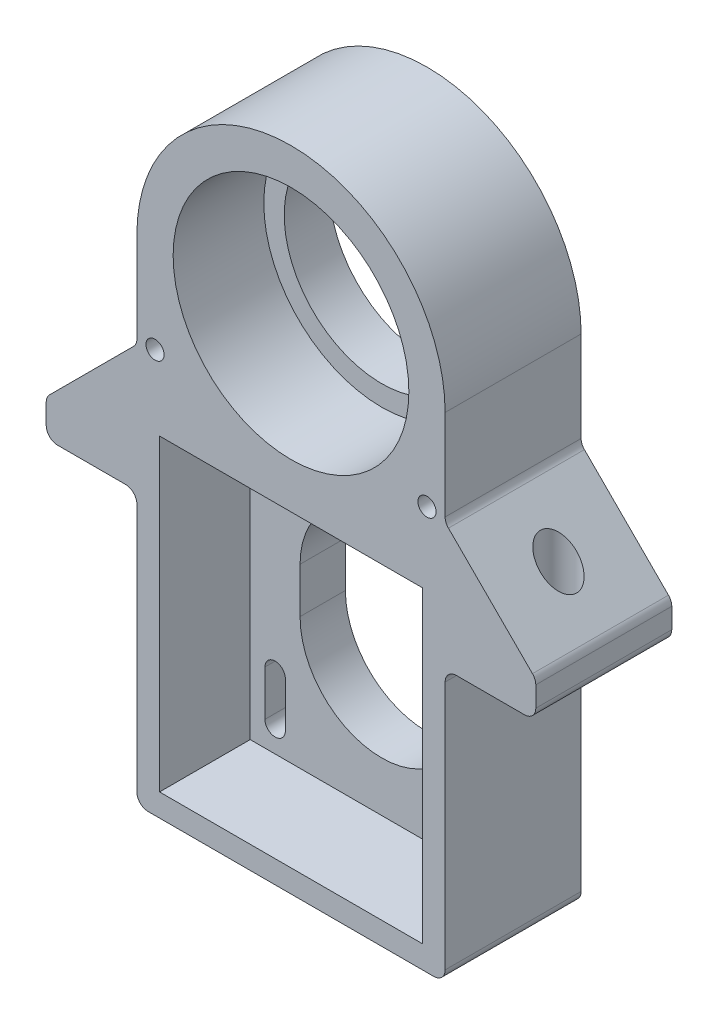
SolidWorks part; units mm, degrees
note: The reader was unsure of these and kept them because the rebuilt part matched: shared geometry of "Esquisse1<4>".
ref_plane "Plan de face" through (0, 0, 0) normal (0, 0, 1) x (1, 0, 0)
ref_plane "Plan de dessus" through (0, 0, 0) normal (0, 1, 0) x (1, 0, 0)
ref_plane "Plan de droite" through (0, 0, 0) normal (1, 0, 0) x (0, 0, -1)
sketch "Esquisse1" plane through (0, 0, 0) normal (0, 0, 1) x (1, 0, 0)
  line L0 (0, 0) -> (0, -75) construction
  line L1 (-34, 0) -> (-34, -41)
  line L2 (29, -104) -> (-29, -104)
  line L3 (29, -104) -> (29, -46)
  line L4 (29, -46) -> (-29, -46)
  line L5 (-29, -104) -> (-29, -46)
  line L6 (29, -104) -> (-29, -46) construction
  line L7 (29, -46) -> (-29, -104) construction
  line L8 (23.5, -98.5) -> (-23.5, -98.5)
  line L9 (23.5, -98.5) -> (23.5, -51.5)
  line L10 (23.5, -51.5) -> (-23.5, -51.5)
  line L11 (-23.5, -98.5) -> (-23.5, -51.5)
  line L12 (23.5, -98.5) -> (-23.5, -51.5) construction
  line L13 (23.5, -51.5) -> (-23.5, -98.5) construction
  line L14 (34, -109) -> (-34, -109)
  line L15 (34, -109) -> (34, -41)
  line L16 (34, -41) -> (-34, -41)
  line L17 (-34, -109) -> (-34, -41)
  line L18 (34, -109) -> (-34, -41) construction
  line L19 (34, -41) -> (-34, -109) construction
  line L20 (34, 0) -> (34, -41)
  line L21 (-34, -41) -> (34, -41)
  line L22 (26, 0) -> (34, -41)
  line L23 (-34, -41) -> (-54, -41)
  line L24 (-34, -41) -> (-34, -49)
  line L25 (-34, -49) -> (-54, -49)
  line L26 (-54, -41) -> (-54, -49)
  line L27 (34, -41) -> (54, -41)
  line L28 (34, -41) -> (34, -49)
  line L29 (34, -49) -> (54, -49)
  line L30 (54, -41) -> (54, -49)
  line L31 (-34, -41) -> (-26, 0)
  line L32 (-26, 0) -> (26, 0)
  line L33 (15, 0) -> (18, -75)
  line L34 (18, -75) -> (-18, -75)
  line L35 (-18, -75) -> (-15, 0)
  line L36 (30.5, 0) -> (18, -75)
  line L37 (-30.5, 0) -> (-18, -75)
  line L38 (-54, -41) -> (-34, -21)
  line L39 (54, -41) -> (34, -21)
  line L40 (23.5, -98.5) -> (23.5, -88.5) construction
  line L41 (21.25, -98.5) -> (21.25, -88.5)
  line L42 (25.75, -98.5) -> (25.75, -88.5)
  line L43 (23.5, -51.5) -> (23.5, -41.5) construction
  line L44 (21.25, -51.5) -> (21.25, -41.5)
  line L45 (25.75, -51.5) -> (25.75, -41.5)
  line L46 (-23.5, -51.5) -> (-23.5, -41.5) construction
  line L47 (-21.25, -51.5) -> (-21.25, -41.5)
  line L48 (-25.75, -51.5) -> (-25.75, -41.5)
  line L49 (-23.5, -98.5) -> (-23.5, -88.5) construction
  line L50 (-21.25, -98.5) -> (-21.25, -88.5)
  line L51 (-25.75, -98.5) -> (-25.75, -88.5)
  line L52 (0, -75) -> (0, -65) construction
  line L53 (-18, -75) -> (-18, -65)
  line L54 (18, -75) -> (18, -65)
  line L56 (29, -46) -> (-29, -46)
  line L57 (29, -46) -> (29, -36)
  line L58 (29, -36) -> (-29, -36)
  line L59 (-29, -46) -> (-29, -36)
  line L60 (34, -41) -> (-34, -41)
  line L61 (34, -41) -> (34, -31)
  line L62 (34, -31) -> (-34, -31)
  line L63 (-34, -41) -> (-34, -31)
  circle A0 centre (0, 0) radius 26
  circle A1 centre (0, 0) radius 34
  circle A2 centre (0, -75) radius 18
  circle A3 centre (0, 0) radius 21.5
  circle A4 centre (23.5, -51.5) radius 2.25
  circle A5 centre (23.5, -98.5) radius 2.25
  circle A6 centre (-23.5, -98.5) radius 2.25
  circle A7 centre (-23.5, -51.5) radius 2.25
  circle A8 centre (0, 0) radius 15
  circle A9 centre (-30, -20) radius 2
  circle A10 centre (30, -20) radius 2
  circle A11 centre (0, 0) radius 30.5
  circle A12 centre (-30, -20) radius 2
  circle A13 centre (30, -20) radius 2
  arc A14 (21.25, -98.5) -> (25.75, -98.5) centre (23.5, -98.5) ccw
  arc A15 (25.75, -88.5) -> (21.25, -88.5) centre (23.5, -88.5) ccw
  arc A16 (21.25, -51.5) -> (25.75, -51.5) centre (23.5, -51.5) ccw
  arc A17 (25.75, -41.5) -> (21.25, -41.5) centre (23.5, -41.5) ccw
  arc A18 (-21.25, -51.5) -> (-25.75, -51.5) centre (-23.5, -51.5) cw
  arc A19 (-25.75, -41.5) -> (-21.25, -41.5) centre (-23.5, -41.5) cw
  arc A20 (-21.25, -98.5) -> (-25.75, -98.5) centre (-23.5, -98.5) cw
  arc A21 (-25.75, -88.5) -> (-21.25, -88.5) centre (-23.5, -88.5) cw
  arc A22 (-18, -75) -> (18, -75) centre (0, -75) ccw
  arc A23 (18, -65) -> (-18, -65) centre (0, -65) ccw
  point P50 (23.5, -93.5)
  point P55 (23.5, -46.5)
  point P62 (-23.5, -46.5)
  point P68 (-23.5, -93.5)
  point P73 (0, -70)
  dimension "D1" = 52
  dimension "D2" = 68
  dimension "D5" = 36
  dimension "D8" = 20
  dimension "D12" = 43
  dimension "D13" = 4.5
  dimension "D14" = 30
  dimension "D15" = 4
  dimension "D18" = 61
  dimension "D3" = 29
  dimension "D4" = 47
  dimension "D6" = 75
  dimension "D7" = 34
  dimension "D9" = 20
  dimension "D10" = 8
  dimension "D11" = 8
  dimension "D16" = 30
  dimension "D17" = 20
  dimension "D19" = 45
  dimension "D20" = 45
  dimension "D21" = 10
  dimension "D22" = 10
  dimension "D23" = 34
  dimension "D24" = 10
  dimension "D25" = 10
extrude "Boss.-Extru.1" add sketch "Esquisse1" along normal blind 20 contours L23 L26 L25 L17 | L38 L23 L1 | L30 L27 L15 L29 | L27 L39 L20 | L5 L59 L16 L17 L14 L15 L57 L3 L2 | L31 L62 L1 | L37 L62 L31 L16 L59 L58 | L35 L62 L37 L58 | A1 L62 L35 L58 L33 | L36 L62 L33 L58 | L22 L62 L36 L58 L57 L16 | L20 L62 L22 | A9 L31 L62 L37 A1 | A1 L37 L62 L35 | A9 L31 A1 L1 L62 | A1 L35 L62 | A1 L62 L33 | A1 L33 L62 L36 | L22 A10 A1 L36 L62 | L22 A10 L62 L20 A1 | A11 L36 L22 A1 L31 L37 | A11 L37 L31 | A11 L31 L37 A1 L35 | L31 A1 L37 | A11 L35 A1 L62 L33 | L62 A1 | A11 L33 A1 L36 L22 | L36 A1 L22 | A11 L22 L36 | L37 A11 L31 A0 L22 L36 | L31 A11 L35 A0 | L35 A11 L33 A0 | L33 A11 L22 A0 | L37 A11 | L36 A11 | L9 L8 L11 L10 | A4 | L54 A23 L53 A22
extrude "Boss.-Extru.2" add sketch "Esquisse1<4>" against normal blind 10 contours A11 L36 L22 A1 L31 L37 | L37 A11 L31 A0 L22 L36 | A3 L32 A0 | A3 L32 A0 L35 | A3 L35 A0 L33 | A3 L33 A0 L32 | L31 A11 L35 A0 | L35 A11 L33 A0 | L33 A11 L22 A0 | A11 L33 A1 L36 L22 | L36 A1 L22 | L22 A10 L62 L20 A1 | L22 A10 A1 L36 L62 | A1 L33 L62 L36 | L27 L39 L20 | A11 L35 A1 L62 L33 | A1 L35 L62 | A1 L37 L62 L35 | A11 L31 L37 A1 L35 | A9 L31 L62 L37 A1 | A9 L31 A1 L1 L62 | L31 A1 L37 | A11 L37 L31 | L37 A11 | A11 L22 L36 | L36 A11 | L35 L4 L33 L21 | L16 A19 L47 L4 L35 | A17 L60 L33 L4 L44 | A17 L45 L4 L57 L21 | L5 L59 L16 L17 L14 L15 L57 L3 L2 | L30 L27 L15 L29 | A23 L10 L33 L4 L35 | L10 L44 L4 L33 | L51 A21 L11 A7 L48 L4 L5 L2 L3 L45 A4 L9 A15 L42 A5 L8 A6 | L47 L10 L35 L4 | L48 A19 L60 L59 L4 | A23 L10 L35 | A23 L35 L10 A7 L37 L53 | L11 A21 L50 L8 L41 A15 L9 A4 L36 A2 L37 A7 | A23 L54 L36 A4 L10 L33 | A23 L33 L10 | L36 A17 L21 | L60 A17 L36 | L20 L62 L22 | A1 L62 L33 | L38 L23 L1 | L23 L26 L25 L17 | L33 L58 L35 L21 | L36 L62 L33 L58 | L22 L62 L36 L58 L57 L16 | L37 A19 L16 L35 L58 | L60 A19 L37 L58 L59 | L37 L62 L31 L16 L59 L58 | L35 L62 L37 L58 | A1 L62 L35 L58 L33 | L62 A1 | L31 L62 L1 | A17 L21 L57 L58 L36 | A17 L36 L58 L33 L60
sketch "Esquisse1<4>" plane through (0, 0, 0) normal (0, 0, 1) x (1, 0, 0) same geometry as "Esquisse1"
sketch "Esquisse2" plane through (0, -49, 0) normal (0, -1, 0) x (1, 0, 0)
  line L0 (0, 36) -> (0, -10) construction
  line L1 (34, 36) -> (-34, 36) construction
  line L2 (34, -10) -> (-34, -10) construction
  line L3 (54, 5) -> (-54, 5) construction
  line L4 (54, 20) -> (54, -10) construction
  line L5 (-54, 20) -> (-54, -10) construction
  circle A3 centre (44, 5) radius 4
  circle A5 centre (-44, 5) radius 4
  dimension "D1" = 8
  dimension "D2" = 0
  dimension "D3" = 10
extrude "Enlèv. mat.-Extru.2" cut sketch "Esquisse2" against normal through all
fillet "Congé1" radius 2.5 10 edges at (34, -21, 5) (-34, -21, 5) (-54, -41, 5) (54, -49, 5) (54, -41, 5) (-54, -49, 5) (-34, -49, 5) (-34, -109, 5) (34, -109, 5) (34, -49, 5)
